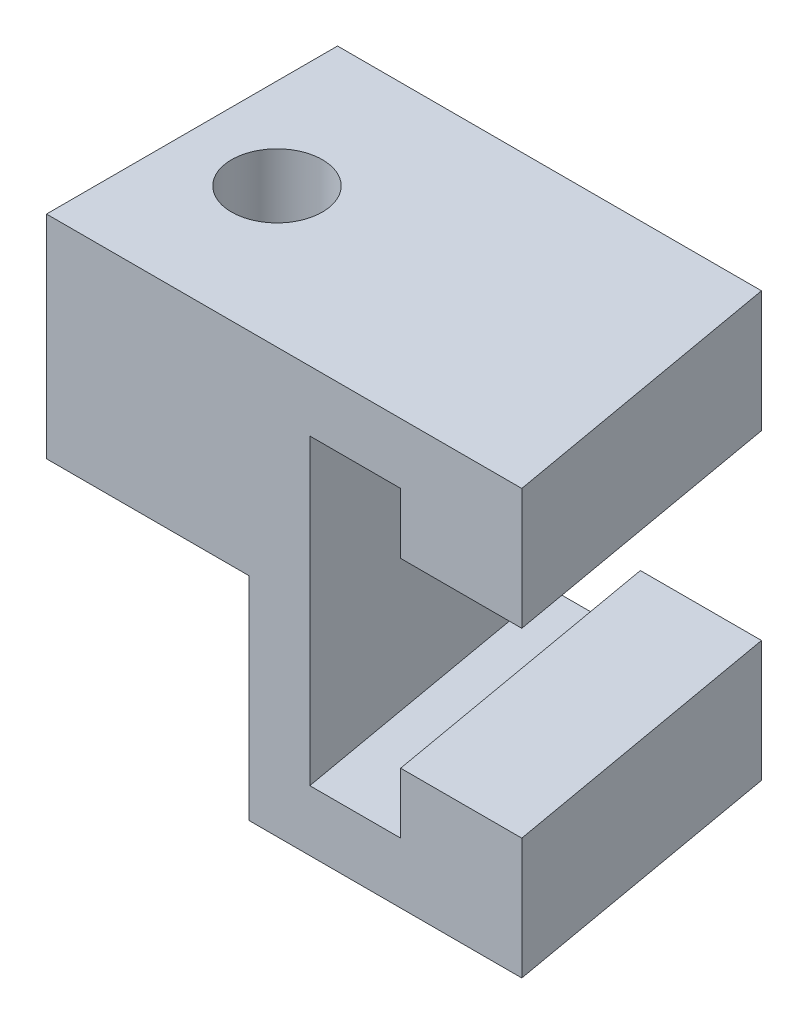
SolidWorks part; units mm, degrees
ref_plane "Front Plane" through (0, 0, 0) normal (0, 0, 1) x (1, 0, 0)
ref_plane "Top Plane" through (0, 0, 0) normal (0, 1, 0) x (1, 0, 0)
ref_plane "Right Plane" through (0, 0, 0) normal (1, 0, 0) x (0, 0, -1)
sketch "Sketch1" plane through (0, 0, 0) normal (0, 0, 1) x (1, 0, 0)
  line L0 (0, 25) -> (0, -25)
  line L1 (0, -25) -> (15, -25)
  line L2 (15, -25) -> (15, -15)
  line L3 (15, -15) -> (35, -15)
  line L4 (35, -15) -> (35, -35)
  line L5 (35, -35) -> (-10, -35)
  line L6 (-10, -35) -> (-10, 35)
  line L12 (0, 0) -> (-10, 0) construction
  line L13 (35, 35) -> (-10, 35)
  line L14 (35, 15) -> (35, 35)
  line L15 (15, 15) -> (35, 15)
  line L16 (15, 25) -> (15, 15)
  line L17 (0, 25) -> (15, 25)
  dimension "D1" = 15
  dimension "D2" = 20
  dimension "D3" = 25
  dimension "D4" = 10
  dimension "D5" = 10
  dimension "D6" = 10
extrude "Boss-Extrude1" [suppressed] add sketch "Sketch1" along normal blind 50
sketch "Sketch3" plane through (0, 0, 0) normal (0, 1, 0) x (1, 0, 0)
  line L0 (-0.3925, -48.0507) -> (55.0633, -48.0507) construction
  line L1 (0, 0) -> (50, 0) construction
  line L2 (55.0633, -48.0507) -> (46.5907, 0)
  point P0 (54.6571, -48.1205)
  dimension "D1" = 80
sweep "Sweep1" add profiles "Sketch1<2>" path "Sketch3"
sketch "Sketch1<2>" plane through (0, 0, 0) normal (0, 0, 1) x (1, 0, 0) same geometry as "Sketch1"
sketch "Sketch4" plane through (0, 0, 0) normal (0, 0, 1) x (1, 0, 0)
  line L0 (-35, 35) -> (0, 35)
  line L1 (0, 35) -> (0, 0)
  line L3 (0, 0) -> (-35, 0)
  line L4 (-35, 0) -> (-35, 35)
  line L6 (43.4726, 35) -> (-1.5274, 35) construction
  point P5 (0, 0)
  point P7 (-52.5913, -35)
  point P8 (0, 0)
  point P9 (0, 0)
  point P11 (0, 0)
  dimension "D1" = 35
extrude "Boss-Extrude2" add sketch "Sketch4" along normal up to surface (48.0507 mm away) up to face at (23.4726, 0, 48.0507)
sketch "Sketch5" plane through (0, 35, 0) normal (0, 1, 0) x (1, 0, 0)
  line L0 (-35, -48.0507) -> (-35, 0) construction
  line L2 (35, 0) -> (-35, 0) construction
  circle A0 centre (-20, -25) radius 7.5
  point P2 (0, 0)
  dimension "D1" = 25
  dimension "D2" = 15
  dimension "D3" = 15
extrude "Cut-Extrude1" cut sketch "Sketch5" against normal blind 44
